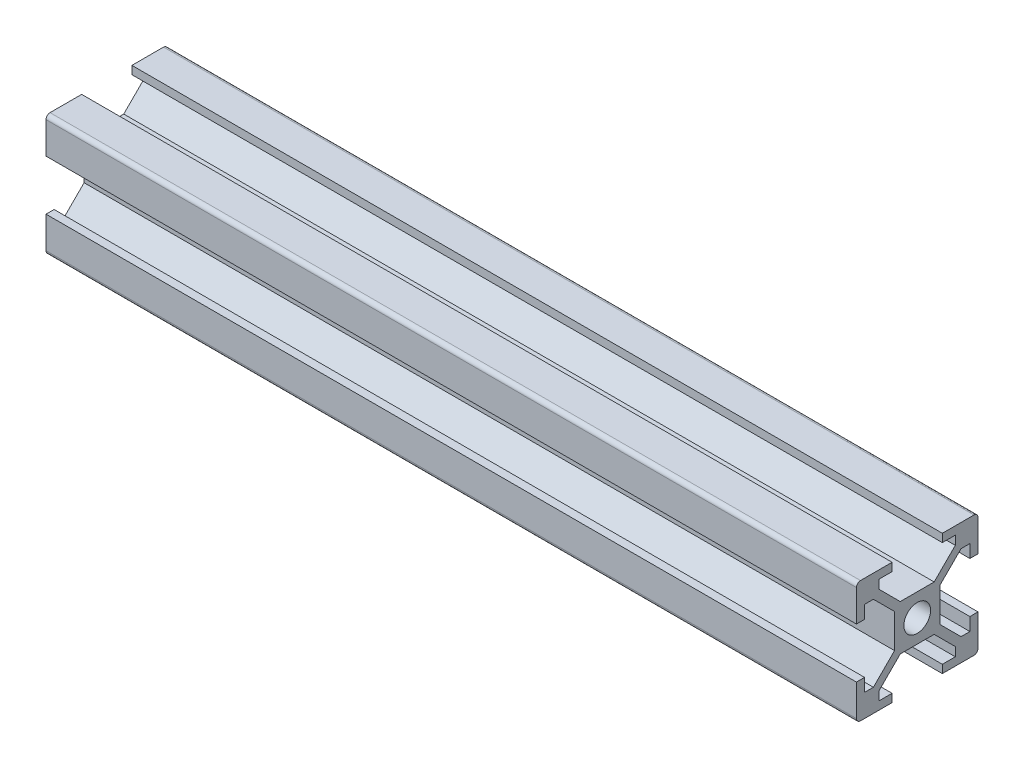
SolidWorks part; units mm, degrees
ref_plane "前视基准面" through (0, 0, 0) normal (0, 0, 1) x (1, 0, 0)
ref_plane "上视基准面" through (0, 0, 0) normal (0, 1, 0) x (1, 0, 0)
ref_plane "右视基准面" through (0, 0, 0) normal (1, 0, 0) x (0, 0, -1)
sketch "草图2" plane through (0, 0, 0) normal (1, 0, 0) x (0, 0, -1)
  line L0 (-3.1, 7.5) -> (3.1, 7.5)
  line L1 (-7, 7.5) -> (7, 7.5)
  line L2 (-7.5, 7) -> (-7.5, -7)
  line L3 (-7, -7.5) -> (7, -7.5)
  line L4 (7.5, 7) -> (7.5, -7)
  line L5 (-3.1, 7.5) -> (-3.1, 6.5)
  line L6 (-3.1, 6.5) -> (-4.7, 6.5)
  line L7 (-4.7, 6.5) -> (-4.7, 5.4071)
  line L8 (-4.7, 5.4071) -> (-2.0929, 2.8)
  line L9 (-2.0929, 2.8) -> (2.0929, 2.8)
  line L10 (2.0929, 2.8) -> (4.7, 5.4071)
  line L11 (4.7, 5.4071) -> (4.7, 6.5)
  line L12 (4.7, 6.5) -> (3.1, 6.5)
  line L13 (3.1, 6.5) -> (3.1, 7.5)
  line L14 (-7.5, -7.5) -> (7.5, 7.5) construction
  line L15 (7.5, -7.5) -> (-7.5, 7.5) construction
  line L17 (-2.8, 2.8) -> (2.8, 2.8)
  line L18 (-2.8, 2.8) -> (-2.8, -2.8)
  line L19 (-2.8, -2.8) -> (2.8, -2.8)
  line L20 (2.8, 2.8) -> (2.8, -2.8)
  line L21 (-2.8, 2.8) -> (2.8, -2.8) construction
  line L22 (-2.8, -2.8) -> (2.8, 2.8) construction
  line L52 (7.5, 3.1) -> (7.5, -3.1)
  line L53 (6.5, -3.1) -> (7.5, -3.1)
  line L54 (6.5, -4.7) -> (6.5, -3.1)
  line L55 (5.4071, -4.7) -> (6.5, -4.7)
  line L56 (2.8, -2.0929) -> (5.4071, -4.7)
  line L57 (2.8, 2.0929) -> (2.8, -2.0929)
  line L58 (5.4071, 4.7) -> (2.8, 2.0929)
  line L59 (6.5, 4.7) -> (5.4071, 4.7)
  line L60 (6.5, 3.1) -> (6.5, 4.7)
  line L61 (7.5, 3.1) -> (6.5, 3.1)
  line L62 (3.1, -7.5) -> (-3.1, -7.5)
  line L63 (-3.1, -6.5) -> (-3.1, -7.5)
  line L64 (-4.7, -6.5) -> (-3.1, -6.5)
  line L65 (-4.7, -5.4071) -> (-4.7, -6.5)
  line L66 (-2.0929, -2.8) -> (-4.7, -5.4071)
  line L67 (2.0929, -2.8) -> (-2.0929, -2.8)
  line L68 (4.7, -5.4071) -> (2.0929, -2.8)
  line L69 (4.7, -6.5) -> (4.7, -5.4071)
  line L70 (3.1, -6.5) -> (4.7, -6.5)
  line L71 (3.1, -7.5) -> (3.1, -6.5)
  line L72 (-7.5, -3.1) -> (-7.5, 3.1)
  line L73 (-6.5, 3.1) -> (-7.5, 3.1)
  line L74 (-6.5, 4.7) -> (-6.5, 3.1)
  line L75 (-5.4071, 4.7) -> (-6.5, 4.7)
  line L76 (-2.8, 2.0929) -> (-5.4071, 4.7)
  line L77 (-2.8, -2.0929) -> (-2.8, 2.0929)
  line L78 (-5.4071, -4.7) -> (-2.8, -2.0929)
  line L79 (-6.5, -4.7) -> (-5.4071, -4.7)
  line L80 (-6.5, -3.1) -> (-6.5, -4.7)
  line L81 (-7.5, -3.1) -> (-6.5, -3.1)
  line L82 (0, 0) -> (2.0929, 2.8) construction
  line L83 (0, 0) -> (2.8, -2.0929) construction
  circle A0 centre (0, 0) radius 1.65
  circle A1 centre (-7, 7) radius 0.5 construction
  circle A2 centre (-7, -7) radius 0.5 construction
  circle A3 centre (7, -7) radius 0.5 construction
  circle A4 centre (7, 7) radius 0.5 construction
  arc A5 (7, 7.5) -> (7.5, 7) centre (7, 7) cw
  arc A6 (7, -7.5) -> (7.5, -7) centre (7, -7) ccw
  arc A7 (-7.5, -7) -> (-7, -7.5) centre (-7, -7) ccw
  arc A8 (-7, 7.5) -> (-7.5, 7) centre (-7, 7) ccw
  point P16 (0, 0)
  point P28 (0, 0)
  point P50 (0, 7.5)
  point P52 (7.5, 0)
  point P62 (-7, -7)
  point P65 (7, -7)
  point P68 (7, 7)
  dimension "D3" = 3.3
  dimension "D12" = 1
  dimension "D13" = 1
  dimension "D14" = 1
  dimension "D15" = 1
  dimension "D16" = 0.5
  dimension "D1" = 15
  dimension "D2" = 6.2
  dimension "D4" = 5.6
  dimension "D5" = 9.4
  dimension "D6" = 0.5
  dimension "D7" = 0.5
  dimension "D8" = 4.7
  dimension "D9" = 1
  dimension "D10" = 4
  dimension "D11" = 90
extrude "凸台-拉伸1" add sketch "草图2" along normal blind 100 contours L2 A7 L3 A6 L4 A5 L1 A8
extrude "切除-拉伸2" cut sketch "草图2<4>" against normal through all and the other way through all contours L3 L71 L70 L69 L68 L19 L66 L65 L64 L63 | L2 L81 L80 L79 L78 L18 L76 L75 L74 L73 | L12 L13 L0 L5 L6 L7 L8 L9 L10 L11 | L4 L61 L60 L59 L58 L20 L56 L55 L54 L53 | A0 region at (0, 5.2713, 0) region at (0, 0, 5.2713) region at (0, 0, -5.2713) region at (0, -5.2713, 0) region at (0, 0, 0)
sketch "草图2<4>" plane through (0, 0, 0) normal (1, 0, 0) x (0, 0, -1) same geometry as "草图2"
